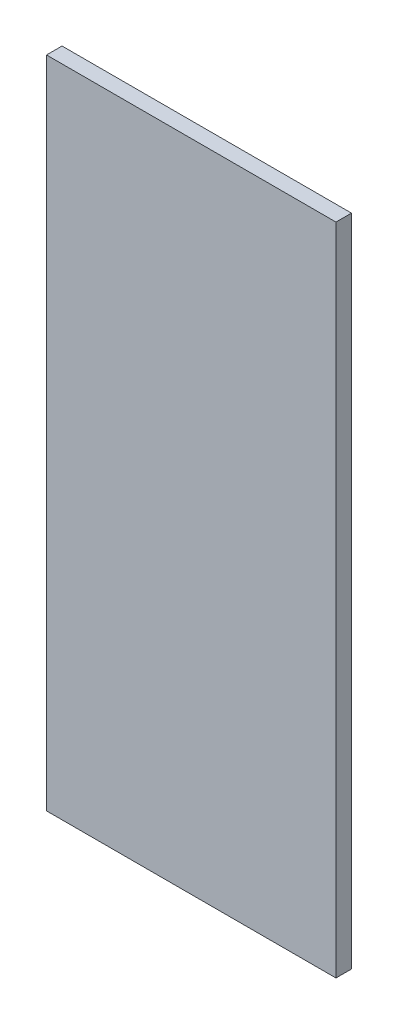
SolidWorks part; units mm, degrees
material "Perspex (TM) GS Acrylic Cast Sheet"
ref_plane "Front Plane" through (0, 0, 0) normal (0, 0, 1) x (1, 0, 0)
ref_plane "Top Plane" through (0, 0, 0) normal (0, 1, 0) x (1, 0, 0)
ref_plane "Right Plane" through (0, 0, 0) normal (1, 0, 0) x (0, 0, -1)
sketch "Sketch1" plane through (0, 0, 0) normal (0, 0, 1) x (1, 0, 0)
  line L1 (-84, -190) -> (84, -190)
  line L2 (-84, -190) -> (-84, 190)
  line L3 (-84, 190) -> (84, 190)
  line L4 (84, -190) -> (84, 190)
  line L5 (-84, -190) -> (84, 190) construction
  line L6 (-84, 190) -> (84, -190) construction
  point P0 (0, 0)
  dimension "D1" = 168
  dimension "D2" = 380
extrude "Boss-Extrude1" add sketch "Sketch1" along normal blind 9
equation "\"PCLength\"= 150mm'Length across I/O from PS to GPU"
equation "\"PCWidth\"= 340mm'Distance of longest part parallel to GPU(ussually GPU)"
equation "\"PCHeight\"= 190mm'Tallest point with mobo laying flat"
equation "\"WallThickness\"= 9mm'Thickness of each outer tank wall"
equation "\"ThermoBarrierThickness\"= 6mm'Thickness of barrier between hot side and cold side"
equation "\"HotSideGap\"= 15mm'Space in the hot side that hot fluid flows into"
equation "\"PCClearance\"= 40mm'Clearance from top of tank to top of PC"
equation "\"RadiatorHeight\"= 277.37mm'Final Height from ground of radiators"
equation "\"D1@Sketch1\"=\"PCLength\" + (2 * \"WallThickness\")"
equation "\"D2@Sketch1\"=\"PCWidth\" + \"PCClearance\""
equation "\"D1@Boss-Extrude1\"=\"WallThickness\""
